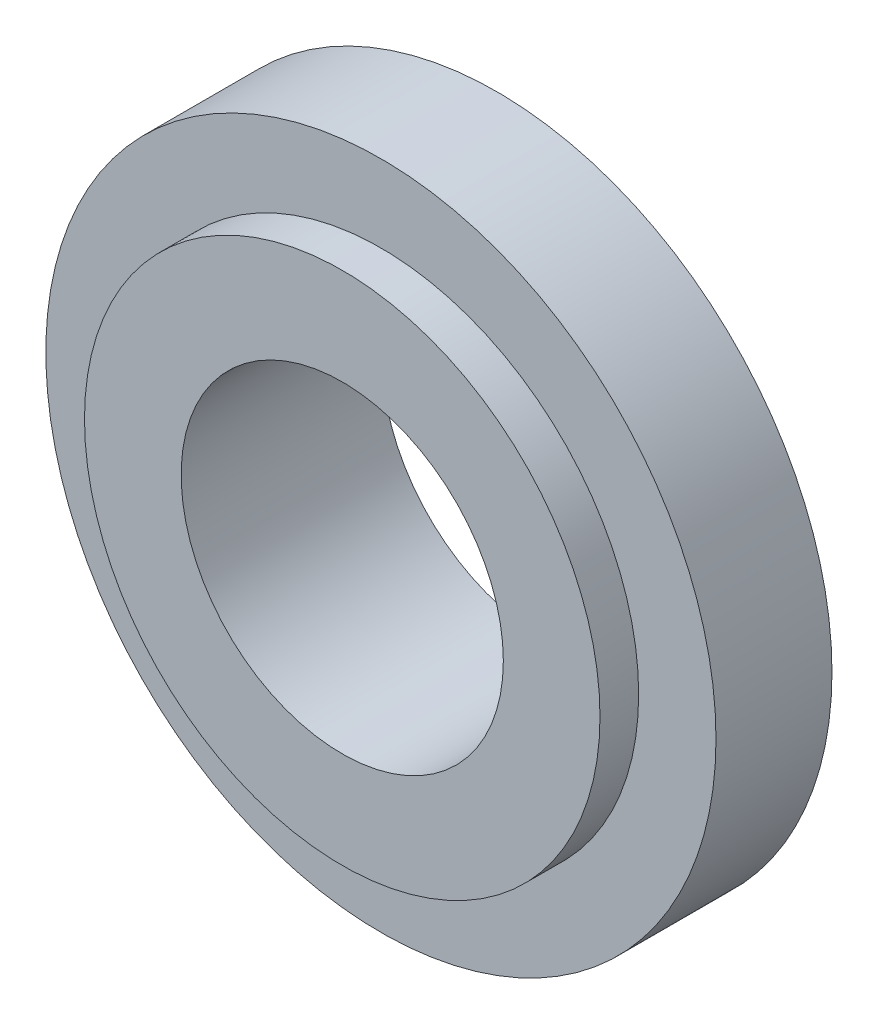
SolidWorks part; units mm, degrees
ref_plane "Front Plane" through (0, 0, 0) normal (0, 0, 1) x (1, 0, 0)
ref_plane "Top Plane" through (0, 0, 0) normal (0, 1, 0) x (1, 0, 0)
ref_plane "Right Plane" through (0, 0, 0) normal (1, 0, 0) x (0, 0, -1)
sketch "Sketch1" plane through (0, 0, 0) normal (0, 0, 1) x (1, 0, 0)
  circle A0 centre (0, 0) radius 7.9375
  circle A1 centre (0, 0) radius 12.7
  dimension "D1" = 15.875
  dimension "D2" = 25.4
extrude "Boss-Extrude1" add sketch "Sketch1" along normal blind 9.906
ref_plane "Plane1" through (0, 0, 5.1435) normal (0, 0, 1) x (1, 0, 0)
sketch "Sketch2" plane through (0, 0, 5.1435) normal (0, 0, 1) x (1, 0, 0)
  circle A0 centre (0, 0) radius 7.9375
  circle A1 centre (0, 0) radius 7.9375 construction
  circle A2 centre (0, 0) radius 16.51
  dimension "D1" = 33.02
extrude "Boss-Extrude2" add sketch "Sketch2" along normal mid plane 5.715
